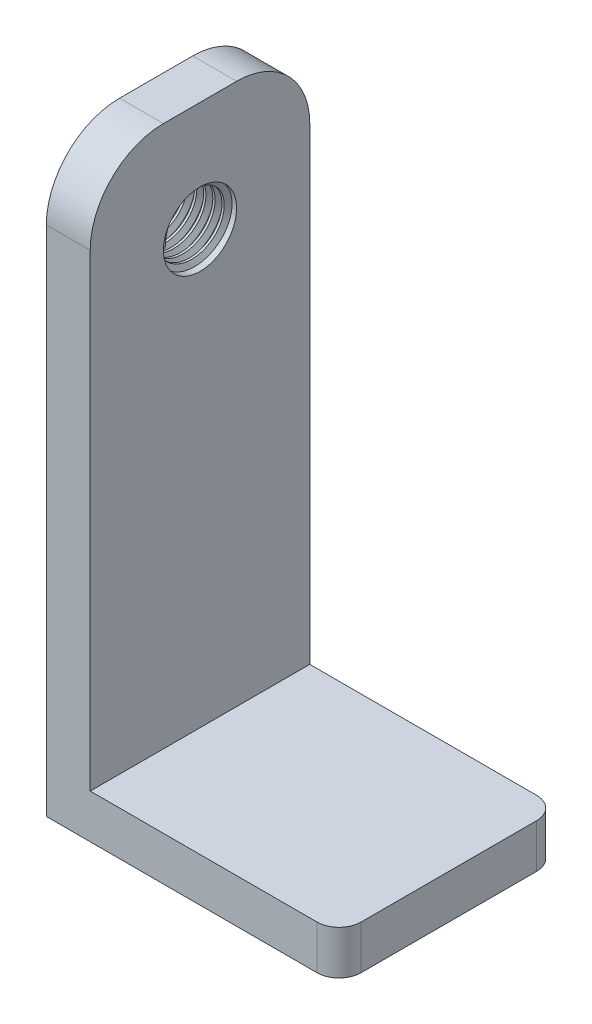
SolidWorks part; units mm, degrees
ref_plane "Front Plane" through (0, 0, 0) normal (0, 0, 1) x (1, 0, 0)
ref_plane "Top Plane" through (0, 0, 0) normal (0, 1, 0) x (1, 0, 0)
ref_plane "Right Plane" through (0, 0, 0) normal (1, 0, 0) x (0, 0, -1)
sketch "Sketch1" plane through (0, 0, 0) normal (0, 0, 1) x (1, 0, 0)
  line L0 (0, 80) -> (0, 0)
  line L1 (0, 0) -> (40, 0)
  line L2 (40, 0) -> (40, 6)
  line L3 (40, 6) -> (6, 6)
  line L4 (6, 6) -> (6, 80)
  line L5 (6, 80) -> (0, 80)
  dimension "D1" = 40
  dimension "D2" = 80
  dimension "D3" = 6
extrude "Boss-Extrude1" add sketch "Sketch1" along normal mid plane 30
sketch "Sketch2" plane through (0, 0, 0) normal (-1, 0, 0) x (0, 0, 1)
  circle A0 centre (0, 65) radius 5
  dimension "D1" = 10
  dimension "D2" = 65
extrude "Cut-Extrude1" cut sketch "Sketch2" against normal blind 30
fillet "Fillet1" radius 10 2 edges at (3, 80, -15) (3, 80, 15)
fillet "Fillet2" radius 3 2 edges at (40, 3, -15) (40, 3, 15)
thread "Thread1" pitch 1.25 method extrude profile "Thread Profile1" start angle 0, offset 0, length 9, pitch 1.25, diameter 10
ref_plane "Plane1" through (6, 65, 5) normal (0, -1, 0) x (0, 0, 1)
sketch "Thread Profile1" plane through (6, 65, 5) normal (0, -1, 0) x (0, 0, 1)
  line L0 (0, 0) -> (0, 1.25) construction
  line L11 (0, 0) -> (0, 1.0937)
  line L12 (0, 1.0937) -> (-0.6766, 0.7031)
  line L13 (-0.6766, 0.7031) -> (-0.6766, 0.3906)
  line L15 (-0.6766, 0.3906) -> (0, 0)
  line L17 (-0.6766, 0.5469) -> (0, 0.5469) construction
  point P2 (0, 0)
  dimension "Pitch" = 1.25
  dimension "Profile_Angle" = 60
  dimension "Profile_Land" = 0.3125
  dimension "Profile_Height" = 0.6766
